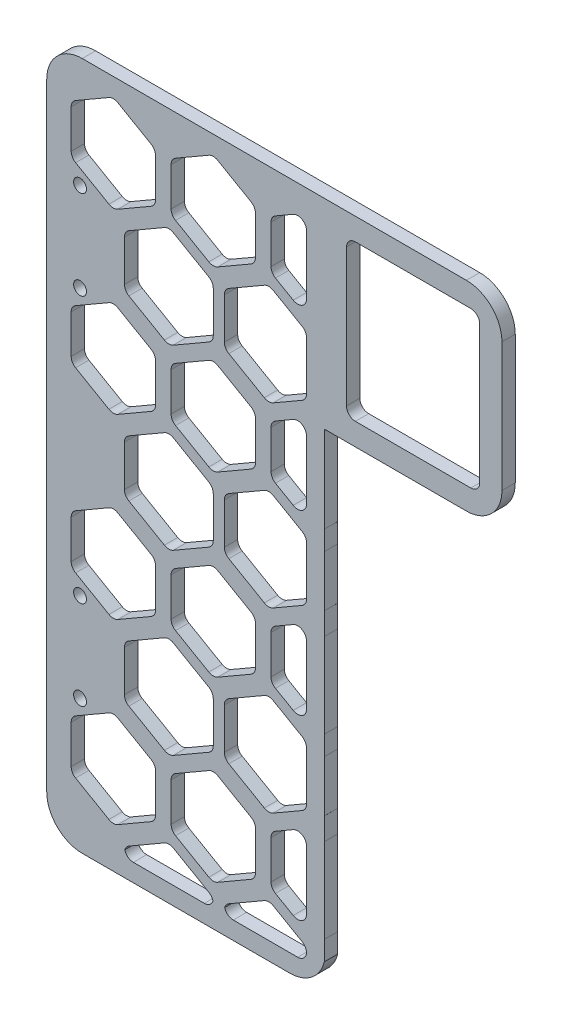
SolidWorks part; units mm, degrees
material "Thornel Mat VMA"
ref_plane "前视基准面" through (0, 0, 0) normal (0, 0, 1) x (1, 0, 0)
ref_plane "上视基准面" through (0, 0, 0) normal (0, 1, 0) x (1, 0, 0)
ref_plane "右视基准面" through (0, 0, 0) normal (1, 0, 0) x (0, 0, -1)
sketch "草图1" plane through (0, 0, 0) normal (0, 0, 1) x (1, 0, 0)
  line L0 (7.5, 0) -> (7.5, 155) construction
  line L1 (0, 0) -> (62.5, 0)
  line L2 (0, 0) -> (0, 155)
  line L3 (0, 155) -> (62.5, 155)
  line L4 (62.5, 0) -> (62.5, 155)
  circle A0 centre (7.5, 30) radius 1.45
  circle A1 centre (7.5, 50) radius 1.45
  circle A2 centre (7.5, 110) radius 1.45
  circle A3 centre (7.5, 130) radius 1.45
  dimension "D1" = 2.9
  dimension "D3" = 30
  dimension "D4" = 20
  dimension "D5" = 20
  dimension "D6" = 25
  dimension "D7" = 60
  dimension "D2" = 7.5
  dimension "D8" = 55
extrude "凸台-拉伸1" add sketch "草图1" along normal blind 3
sketch "草图3" plane through (0, 0, 3) normal (0, 0, 1) x (1, 0, 0)
  line L12 (0, 155) -> (0, 0) construction
  line L13 (15, 150.9697) -> (5.5, 145.4848)
  line L14 (5.5, 145.4848) -> (5.5, 134.5152)
  line L15 (5.5, 134.5152) -> (15, 129.0303)
  line L16 (15, 129.0303) -> (24.5, 134.5152)
  line L17 (24.5, 134.5152) -> (24.5, 145.4848)
  line L18 (24.5, 145.4848) -> (15, 150.9697)
  line L19 (27.4945, 131.8632) -> (17.4945, 126.0897)
  line L20 (17.4945, 126.0897) -> (17.4945, 114.5427)
  line L21 (17.4945, 114.5427) -> (27.4945, 108.7692)
  line L22 (27.4945, 108.7692) -> (37.4945, 114.5427)
  line L23 (37.4945, 114.5427) -> (37.4945, 126.0897)
  line L24 (37.4945, 126.0897) -> (27.4945, 131.8632)
  line L25 (62.5, 155) -> (0, 155) construction
  line L26 (37.5, 150.9697) -> (28, 145.4848)
  line L27 (28, 145.4848) -> (28, 134.5152)
  line L28 (28, 134.5152) -> (37.5, 129.0303)
  line L29 (37.5, 129.0303) -> (47, 134.5152)
  line L30 (47, 134.5152) -> (47, 145.4848)
  line L31 (47, 145.4848) -> (37.5, 150.9697)
  line L32 (49.9945, 131.8632) -> (39.9945, 126.0897)
  line L33 (39.9945, 126.0897) -> (39.9945, 114.5427)
  line L34 (39.9945, 114.5427) -> (49.9945, 108.7692)
  line L35 (49.9945, 108.7692) -> (59.9945, 114.5427)
  line L36 (59.9945, 114.5427) -> (59.9945, 126.0897)
  line L37 (59.9945, 126.0897) -> (49.9945, 131.8632)
  line L38 (37.5, 110.9697) -> (28, 105.4848)
  line L39 (28, 105.4848) -> (28, 94.5152)
  line L40 (28, 94.5152) -> (37.5, 89.0303)
  line L41 (37.5, 89.0303) -> (47, 94.5152)
  line L42 (47, 94.5152) -> (47, 105.4848)
  line L43 (47, 105.4848) -> (37.5, 110.9697)
  line L44 (49.9945, 91.8632) -> (39.9945, 86.0897)
  line L45 (39.9945, 86.0897) -> (39.9945, 74.5427)
  line L46 (39.9945, 74.5427) -> (49.9945, 68.7692)
  line L47 (49.9945, 68.7692) -> (59.9945, 74.5427)
  line L48 (59.9945, 74.5427) -> (59.9945, 86.0897)
  line L49 (59.9945, 86.0897) -> (49.9945, 91.8632)
  line L50 (37.5, 70.9697) -> (28, 65.4848)
  line L51 (28, 65.4848) -> (28, 54.5152)
  line L52 (28, 54.5152) -> (37.5, 49.0303)
  line L53 (37.5, 49.0303) -> (47, 54.5152)
  line L54 (47, 54.5152) -> (47, 65.4848)
  line L55 (47, 65.4848) -> (37.5, 70.9697)
  line L56 (49.9945, 51.8632) -> (39.9945, 46.0897)
  line L57 (39.9945, 46.0897) -> (39.9945, 34.5427)
  line L58 (39.9945, 34.5427) -> (49.9945, 28.7692)
  line L59 (49.9945, 28.7692) -> (59.9945, 34.5427)
  line L60 (59.9945, 34.5427) -> (59.9945, 46.0897)
  line L61 (59.9945, 46.0897) -> (49.9945, 51.8632)
  line L62 (15, 110.9697) -> (5.5, 105.4848)
  line L63 (5.5, 105.4848) -> (5.5, 94.5152)
  line L64 (5.5, 94.5152) -> (15, 89.0303)
  line L65 (15, 89.0303) -> (24.5, 94.5152)
  line L66 (24.5, 94.5152) -> (24.5, 105.4848)
  line L67 (24.5, 105.4848) -> (15, 110.9697)
  line L68 (27.4945, 91.8632) -> (17.4945, 86.0897)
  line L69 (17.4945, 86.0897) -> (17.4945, 74.5427)
  line L70 (17.4945, 74.5427) -> (27.4945, 68.7692)
  line L71 (27.4945, 68.7692) -> (37.4945, 74.5427)
  line L72 (37.4945, 74.5427) -> (37.4945, 86.0897)
  line L73 (37.4945, 86.0897) -> (27.4945, 91.8632)
  line L74 (15, 70.9697) -> (5.5, 65.4848)
  line L75 (5.5, 65.4848) -> (5.5, 54.5152)
  line L76 (5.5, 54.5152) -> (15, 49.0303)
  line L77 (15, 49.0303) -> (24.5, 54.5152)
  line L78 (24.5, 54.5152) -> (24.5, 65.4848)
  line L79 (24.5, 65.4848) -> (15, 70.9697)
  line L80 (27.4945, 51.8632) -> (17.4945, 46.0897)
  line L81 (17.4945, 46.0897) -> (17.4945, 34.5427)
  line L82 (17.4945, 34.5427) -> (27.4945, 28.7692)
  line L83 (27.4945, 28.7692) -> (37.4945, 34.5427)
  line L84 (37.4945, 34.5427) -> (37.4945, 46.0897)
  line L85 (37.4945, 46.0897) -> (27.4945, 51.8632)
  line L110 (60, 150.9697) -> (50.5, 145.4848)
  line L111 (50.5, 145.4848) -> (50.5, 134.5152)
  line L112 (50.5, 134.5152) -> (60, 129.0303)
  line L113 (60, 129.0303) -> (69.5, 134.5152)
  line L114 (69.5, 134.5152) -> (69.5, 145.4848)
  line L115 (69.5, 145.4848) -> (60, 150.9697)
  line L116 (72.4945, 131.8632) -> (62.4945, 126.0897)
  line L117 (62.4945, 126.0897) -> (62.4945, 114.5427)
  line L118 (62.4945, 114.5427) -> (72.4945, 108.7692)
  line L119 (72.4945, 108.7692) -> (82.4945, 114.5427)
  line L120 (82.4945, 114.5427) -> (82.4945, 126.0897)
  line L121 (82.4945, 126.0897) -> (72.4945, 131.8632)
  line L122 (60, 110.9697) -> (50.5, 105.4848)
  line L123 (50.5, 105.4848) -> (50.5, 94.5152)
  line L124 (50.5, 94.5152) -> (60, 89.0303)
  line L125 (60, 89.0303) -> (69.5, 94.5152)
  line L126 (69.5, 94.5152) -> (69.5, 105.4848)
  line L127 (69.5, 105.4848) -> (60, 110.9697)
  line L128 (72.4945, 91.8632) -> (62.4945, 86.0897)
  line L129 (62.4945, 86.0897) -> (62.4945, 74.5427)
  line L130 (62.4945, 74.5427) -> (72.4945, 68.7692)
  line L131 (72.4945, 68.7692) -> (82.4945, 74.5427)
  line L132 (82.4945, 74.5427) -> (82.4945, 86.0897)
  line L133 (82.4945, 86.0897) -> (72.4945, 91.8632)
  line L134 (60, 70.9697) -> (50.5, 65.4848)
  line L135 (50.5, 65.4848) -> (50.5, 54.5152)
  line L136 (50.5, 54.5152) -> (60, 49.0303)
  line L137 (60, 49.0303) -> (69.5, 54.5152)
  line L138 (69.5, 54.5152) -> (69.5, 65.4848)
  line L139 (69.5, 65.4848) -> (60, 70.9697)
  line L140 (72.4945, 51.8632) -> (62.4945, 46.0897)
  line L141 (62.4945, 46.0897) -> (62.4945, 34.5427)
  line L142 (62.4945, 34.5427) -> (72.4945, 28.7692)
  line L143 (72.4945, 28.7692) -> (82.4945, 34.5427)
  line L144 (82.4945, 34.5427) -> (82.4945, 46.0897)
  line L145 (82.4945, 46.0897) -> (72.4945, 51.8632)
  line L146 (15, 30.9697) -> (5.5, 25.4848)
  line L147 (5.5, 25.4848) -> (5.5, 14.5152)
  line L148 (5.5, 14.5152) -> (15, 9.0303)
  line L149 (15, 9.0303) -> (24.5, 14.5152)
  line L150 (24.5, 14.5152) -> (24.5, 25.4848)
  line L151 (24.5, 25.4848) -> (15, 30.9697)
  line L152 (27.4945, 11.8632) -> (17.4945, 6.0897)
  line L153 (17.4945, 6.0897) -> (17.4945, -5.4573)
  line L154 (17.4945, -5.4573) -> (27.4945, -11.2308)
  line L155 (27.4945, -11.2308) -> (37.4945, -5.4573)
  line L156 (37.4945, -5.4573) -> (37.4945, 6.0897)
  line L157 (37.4945, 6.0897) -> (27.4945, 11.8632)
  line L158 (37.5, 30.9697) -> (28, 25.4848)
  line L159 (28, 25.4848) -> (28, 14.5152)
  line L160 (28, 14.5152) -> (37.5, 9.0303)
  line L161 (37.5, 9.0303) -> (47, 14.5152)
  line L162 (47, 14.5152) -> (47, 25.4848)
  line L163 (47, 25.4848) -> (37.5, 30.9697)
  line L164 (49.9945, 11.8632) -> (39.9945, 6.0897)
  line L165 (39.9945, 6.0897) -> (39.9945, -5.4573)
  line L166 (39.9945, -5.4573) -> (49.9945, -11.2308)
  line L167 (49.9945, -11.2308) -> (59.9945, -5.4573)
  line L168 (59.9945, -5.4573) -> (59.9945, 6.0897)
  line L169 (59.9945, 6.0897) -> (49.9945, 11.8632)
  line L170 (60, 30.9697) -> (50.5, 25.4848)
  line L171 (50.5, 25.4848) -> (50.5, 14.5152)
  line L172 (50.5, 14.5152) -> (60, 9.0303)
  line L173 (60, 9.0303) -> (69.5, 14.5152)
  line L174 (69.5, 14.5152) -> (69.5, 25.4848)
  line L175 (69.5, 25.4848) -> (60, 30.9697)
  line L176 (72.4945, 11.8632) -> (62.4945, 6.0897)
  line L177 (62.4945, 6.0897) -> (62.4945, -5.4573)
  line L178 (62.4945, -5.4573) -> (72.4945, -11.2308)
  line L179 (72.4945, -11.2308) -> (82.4945, -5.4573)
  line L180 (82.4945, -5.4573) -> (82.4945, 6.0897)
  line L181 (82.4945, 6.0897) -> (72.4945, 11.8632)
  circle A0 centre (15, 140) radius 9.5 construction
  circle A1 centre (27.4945, 120.3162) radius 10 construction
  circle A2 centre (37.5, 140) radius 9.5 construction
  circle A3 centre (49.9945, 120.3162) radius 10 construction
  circle A4 centre (37.5, 100) radius 9.5 construction
  circle A5 centre (49.9945, 80.3162) radius 10 construction
  circle A6 centre (37.5, 60) radius 9.5 construction
  circle A7 centre (49.9945, 40.3162) radius 10 construction
  circle A8 centre (15, 100) radius 9.5 construction
  circle A9 centre (27.4945, 80.3162) radius 10 construction
  circle A10 centre (15, 60) radius 9.5 construction
  circle A11 centre (27.4945, 40.3162) radius 10 construction
  circle A12 centre (60, 140) radius 9.5 construction
  circle A13 centre (72.4945, 120.3162) radius 10 construction
  circle A14 centre (60, 100) radius 9.5 construction
  circle A15 centre (72.4945, 80.3162) radius 10 construction
  circle A16 centre (60, 60) radius 9.5 construction
  circle A17 centre (72.4945, 40.3162) radius 10 construction
  circle A18 centre (15, 20) radius 9.5 construction
  circle A19 centre (27.4945, 0.3162) radius 10 construction
  circle A20 centre (37.5, 20) radius 9.5 construction
  circle A21 centre (49.9945, 0.3162) radius 10 construction
  circle A22 centre (60, 20) radius 9.5 construction
  circle A23 centre (72.4945, 0.3162) radius 10 construction
  point P20 (0, 0)
  point P21 (0, 0)
  point P22 (0, 0)
  dimension "D1" = 19
  dimension "D2" = 20
  dimension "D3" = 4
  dimension "D4" = 15
  dimension "2" = 2.9945
  dimension "D5" = 15
  dimension "D8" = 40
  dimension "D9" = 22.5
  dimension "D6" = 3
  dimension "D7" = 4
extrude "切除-拉伸1" cut sketch "草图3" against normal blind 3
sketch "草图5" plane through (0, 0, 3) normal (0, 0, 1) x (1, 0, 0)
  line L0 (62.5, 155) -> (62.4945, 0)
  line L1 (62.4945, 0) -> (8.7473, 0)
  line L2 (0, 0) -> (17.4945, 0) construction
  line L3 (8.7473, 0) -> (8.7473, 4)
  line L4 (8.7473, 4) -> (58.5, 4)
  line L5 (58.5, 4) -> (58.5, 155)
  line L6 (62.5, 155) -> (0, 155) construction
  line L7 (58.5, 155) -> (62.5, 155)
  dimension "D1" = 4
  dimension "D2" = 4
extrude "凸台-拉伸3" add sketch "草图5" against normal blind 3
sketch "草图6" plane through (0, 0, 0) normal (0, 0, 1) x (1, 0, 0)
  line L0 (62.5, 155) -> (102.4984, 155)
  line L1 (102.4984, 155) -> (102.4984, 110)
  line L2 (102.4984, 110) -> (62.4984, 110)
  line L3 (62.4977, 90.4724) -> (62.4984, 109.5272) construction
  line L4 (62.4984, 110) -> (62.5, 155)
  line L5 (67.4986, 115) -> (67.4998, 150)
  line L6 (67.4998, 150) -> (97.4984, 150)
  line L7 (97.4984, 150) -> (97.4984, 115)
  line L8 (97.4984, 115) -> (67.4986, 115)
  dimension "D2" = 45
  dimension "D3" = 40
  dimension "D1" = 5
extrude "凸台-拉伸4" add sketch "草图6" along normal blind 3
fillet "圆角1" radius 8 5 edges at (62.4945, 0, 1.5) (0, 0, 1.5) (0, 155, 1.5) (102.4984, 155, 1.5) (102.4984, 110, 1.5)
fillet "圆角2" radius 2 114 edges at (67.4998, 150, 1.5) (97.4984, 150, 1.5) (97.4984, 115, 1.5) (67.4986, 115, 1.5) (24.5, 145.4848, 1.5) (24.5, 134.5152, 1.5) (15, 129.0303, 1.5) (5.5, 134.5152, 1.5) (5.5, 145.4848, 1.5) (15, 150.9697, 1.5) (47, 25.4848, 1.5) (47, 14.5152, 1.5) (37.5, 9.0303, 1.5) (28, 14.5152, 1.5) (28, 25.4848, 1.5) (37.5, 30.9697, 1.5) (24.5, 25.4848, 1.5) (24.5, 14.5152, 1.5) (15, 9.0303, 1.5) (5.5, 14.5152, 1.5) (5.5, 25.4848, 1.5) (15, 30.9697, 1.5) (47, 65.4848, 1.5) (47, 54.5152, 1.5) (37.5, 49.0303, 1.5) (28, 54.5152, 1.5) (28, 65.4848, 1.5) (37.5, 70.9697, 1.5) (24.5, 105.4848, 1.5) (24.5, 94.5152, 1.5) (15, 89.0303, 1.5) (5.5, 94.5152, 1.5) (5.5, 105.4848, 1.5) (47, 145.4848, 1.5) (47, 134.5152, 1.5) (37.5, 129.0303, 1.5) (28, 134.5152, 1.5) (28, 145.4848, 1.5) (37.5, 150.9697, 1.5) (37.4945, 126.0897, 1.5) (37.4945, 114.5427, 1.5) (27.4945, 108.7692, 1.5) (17.4945, 114.5427, 1.5) (17.4945, 126.0897, 1.5) (27.4945, 131.8632, 1.5) (47, 105.4848, 1.5) (47, 94.5152, 1.5) (37.5, 89.0303, 1.5) (28, 94.5152, 1.5) (28, 105.4848, 1.5) (37.5, 110.9697, 1.5) (24.5, 65.4848, 1.5) (24.5, 54.5152, 1.5) (15, 49.0303, 1.5) (5.5, 54.5152, 1.5) (5.5, 65.4848, 1.5) (15, 70.9697, 1.5) (37.4945, 86.0897, 1.5) (37.4945, 74.5427, 1.5) (27.4945, 68.7692, 1.5) (17.4945, 74.5427, 1.5) (17.4945, 86.0897, 1.5) (27.4945, 91.8632, 1.5) (37.4945, 46.0897, 1.5) (37.4945, 34.5427, 1.5) (27.4945, 28.7692, 1.5) (17.4945, 34.5427, 1.5) (17.4945, 46.0897, 1.5) (27.4945, 51.8632, 1.5) (50.5, 134.5152, 1.5) (50.5, 145.4848, 1.5) (58.5, 150.1036, 1.5) (58.5, 129.8964, 1.5) (49.9945, 108.7692, 1.5) (39.9945, 114.5427, 1.5) (39.9945, 126.0897, 1.5) (49.9945, 131.8632, 1.5) (58.5, 126.9526, 1.5) (58.5, 113.6798, 1.5) (50.5, 94.5152, 1.5) (50.5, 105.4848, 1.5) (58.5, 110.1036, 1.5) (58.5, 89.8964, 1.5) (49.9945, 68.7692, 1.5) (39.9945, 74.5427, 1.5) (39.9945, 86.0897, 1.5) (49.9945, 91.8632, 1.5) (58.5, 86.9526, 1.5) (58.5, 73.6798, 1.5) (50.5, 54.5152, 1.5) (50.5, 65.4848, 1.5) (58.5, 70.1036, 1.5) (58.5, 49.8964, 1.5) (49.9945, 28.7692, 1.5) (39.9945, 34.5427, 1.5) (39.9945, 46.0897, 1.5) (49.9945, 51.8632, 1.5) (58.5, 46.9526, 1.5) (58.5, 33.6798, 1.5) (50.5, 14.5152, 1.5) (50.5, 25.4848, 1.5) (58.5, 30.1036, 1.5) (58.5, 9.8964, 1.5) (39.9945, 6.0897, 1.5) (49.9945, 11.8632, 1.5) (58.5, 6.9526, 1.5) (58.5, 4, 1.5) (39.9945, 4, 1.5) (17.4945, 6.0897, 1.5) (27.4945, 11.8632, 1.5) (37.4945, 6.0897, 1.5) (37.4945, 4, 1.5) (17.4945, 4, 1.5) (15, 110.9697, 1.5)
